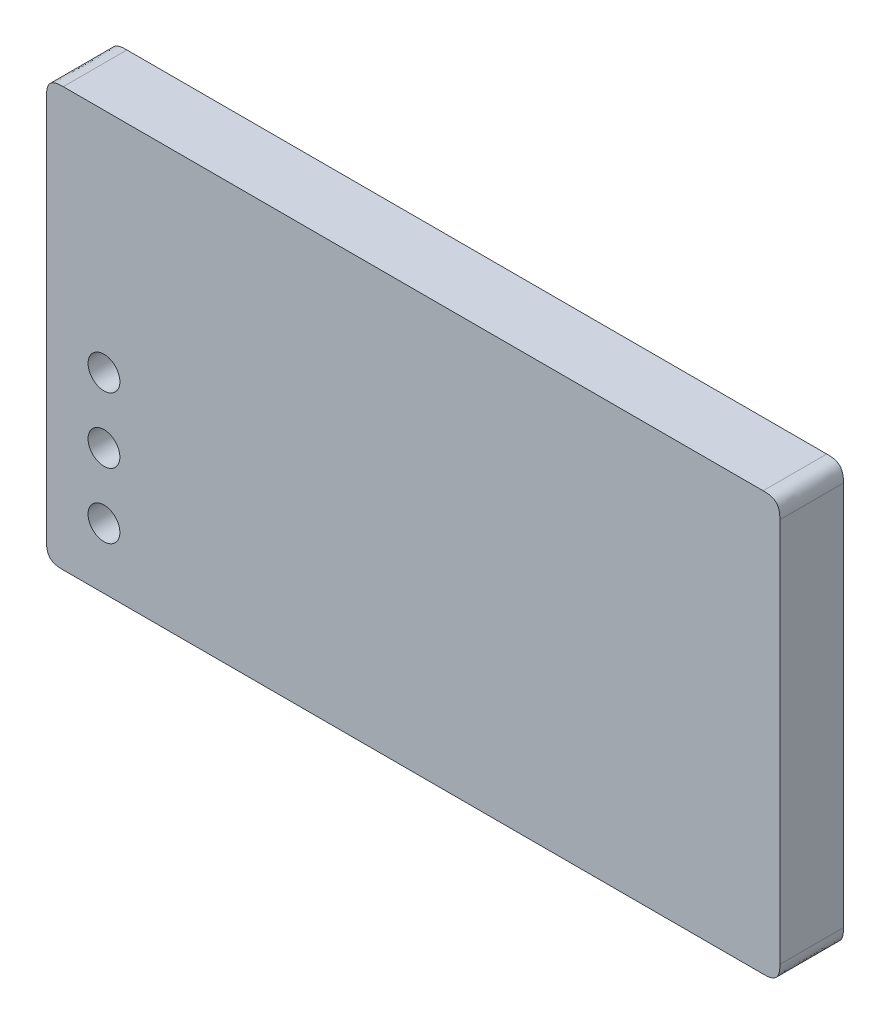
SolidWorks part; units mm, degrees
ref_plane "Plan de face" through (0, 0, 0) normal (0, 0, 1) x (1, 0, 0)
ref_plane "Plan de dessus" through (0, 0, 0) normal (0, 1, 0) x (1, 0, 0)
ref_plane "Plan de droite" through (0, 0, 0) normal (1, 0, 0) x (0, 0, -1)
sketch "Esquisse1" plane through (0, 0, 0) normal (0, 0, 1) x (1, 0, 0)
  line L1 (0, 0) -> (219, 0)
  line L2 (0, 0) -> (0, 125)
  line L3 (0, 125) -> (219, 125)
  line L4 (219, 0) -> (219, 125)
  line L5 (2.26, 2.26) -> (216.74, 2.26)
  line L6 (2.26, 2.26) -> (2.26, 122.74)
  line L7 (2.26, 122.74) -> (216.74, 122.74)
  line L8 (216.74, 2.26) -> (216.74, 122.74)
  dimension "D1" = 219
  dimension "D2" = 125
  dimension "D3" = 2.26
  dimension "D4" = 2.26
  dimension "D5" = 2.26
  dimension "D6" = 2.26
extrude "Boss.-Extru.1" add sketch "Esquisse1" along normal blind 19 contours L3 L4 L1 L2
sketch "Esquisse3" plane through (0, 0, 0) normal (0, 0, -1) x (-1, 0, 0)
  line L0 (-219, 0) -> (-219, 125) construction
  line L1 (-216.4, 122.4) -> (-2.6, 122.4)
  line L2 (-216.4, 122.4) -> (-216.4, 2.6)
  line L3 (-216.4, 2.6) -> (-2.6, 2.6)
  line L4 (-2.6, 122.4) -> (-2.6, 2.6)
  line L5 (0, 125) -> (-219, 125) construction
  line L6 (0, 0) -> (-219, 0) construction
  line L7 (0, 0) -> (0, 125) construction
  dimension "D1" = 2.6
  dimension "D2" = 2.6
  dimension "D3" = 2.6
  dimension "D4" = 2.6
extrude "Enlèv. mat.-Extru.1" cut sketch "Esquisse3" against normal blind 7.7
sketch "Esquisse4" plane through (0, 0, 19) normal (0, 0, 1) x (1, 0, 0)
  line L0 (0, 0) -> (0, 125) construction
  line L1 (0, 0) -> (219, 0) construction
  circle A0 centre (17.15, 57.15) radius 4.75
  circle A1 centre (17.15, 37.65) radius 4.75
  circle A2 centre (17.15, 18.15) radius 4.75
  dimension "D1" = 9.5
  dimension "D2" = 17.15
  dimension "D3" = 57.15
  dimension "D4" = 3
extrude "Enlèv. mat.-Extru.2" cut sketch "Esquisse4" against normal through all
fillet "Congé4" radius 5 1 edges at (219, 0, 9.5) curvature continuous yes
fillet "Congé5" radius 5 3 edges at (0, 125, 9.5) (0, 0, 9.5) (219, 125, 9.5) curvature continuous yes
